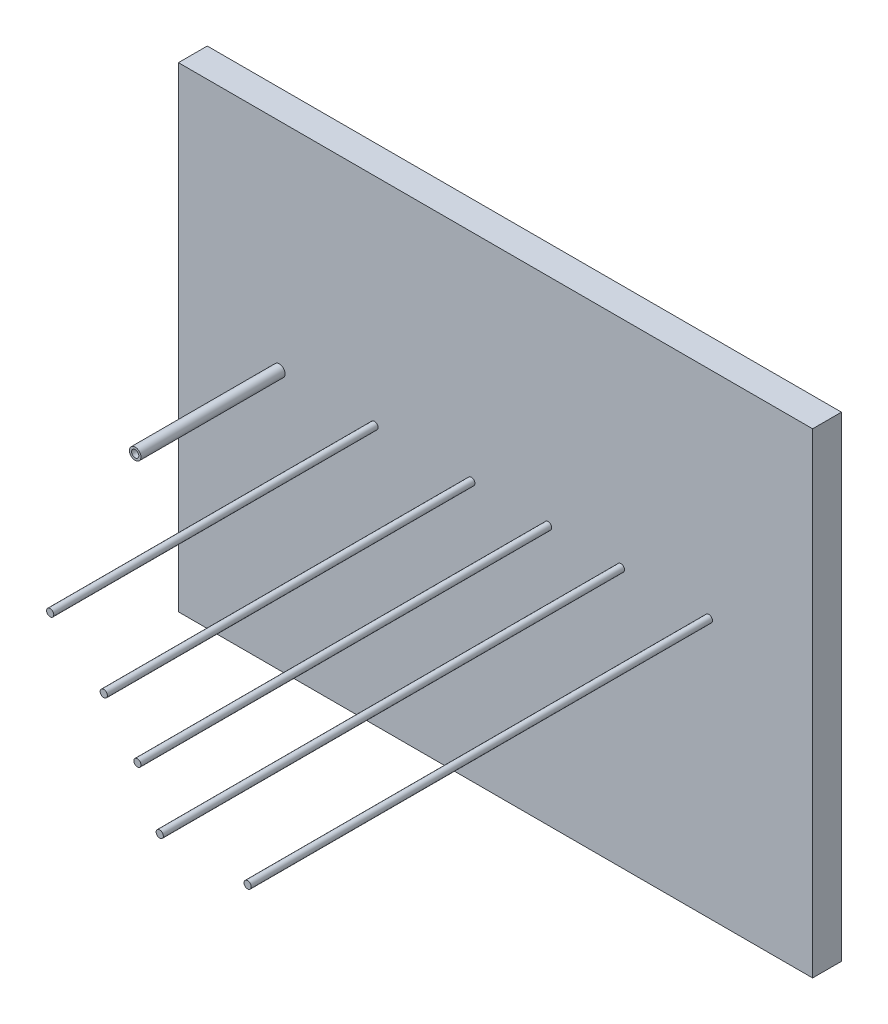
SolidWorks part; units mm, degrees
ref_plane "Alzado" through (0, 0, 0) normal (0, 0, 1) x (1, 0, 0)
ref_plane "Planta" through (0, 0, 0) normal (0, 1, 0) x (1, 0, 0)
ref_plane "Vista lateral" through (0, 0, 0) normal (1, 0, 0) x (0, 0, -1)
sketch "Croquis1" plane through (0, 0, 0) normal (0, 0, 1) x (1, 0, 0)
  line L1 (0, 0) -> (440, 0)
  line L2 (0, 0) -> (0, 330)
  line L3 (0, 330) -> (440, 330)
  line L4 (440, 0) -> (440, 330)
  line L5 (0, 0) -> (440, 330) construction
  line L6 (0, 330) -> (440, 0) construction
  point P4 (220, 165)
  dimension "D1" = 330
  dimension "D2" = 440
extrude "Saliente-Extruir1" add sketch "Croquis1" along normal blind 20
sketch "Croquis3" plane through (0, 0, 20) normal (0, 0, 1) x (1, 0, 0)
  line L0 (0, 0) -> (440, 0) construction
  line L1 (0, 330) -> (0, 0) construction
  circle A0 centre (70, 180) radius 4
  circle A1 centre (136, 180) radius 2.5
  circle A2 centre (203.2, 180) radius 2.5
  circle A4 centre (256.5, 180) radius 2.5
  circle A5 centre (307, 180) radius 2.5
  circle A6 centre (368, 180) radius 2.5
  dimension "D1" = 8
  dimension "D2" = 5
  dimension "D3" = 5
  dimension "D4" = 5
  dimension "D10" = 5
  dimension "D12" = 5
  dimension "D5" = 66
  dimension "D6" = 67.2
  dimension "D8" = 180
  dimension "D7" = 53.3
  dimension "D9" = 70
  dimension "D11" = 50.5
  dimension "D13" = 61
extrude "Saliente-Extruir2" add sketch "Croquis3" along normal blind 100 contours A0 region at (70, 180, 20)
sketch "Croquis5" plane through (0, 0, 120) normal (0, 0, 1) x (1, 0, 0)
  circle A0 centre (70, 180) radius 2.5
  dimension "D1" = 5
extrude "Cortar-Extruir2" cut sketch "Croquis5" against normal blind 100
extrude "Saliente-Extruir3" add sketch "Croquis3<3>" along normal blind 225 contours A1
sketch "Croquis3<3>" plane through (0, 0, 20) normal (0, 0, 1) x (1, 0, 0) same geometry as "Croquis3"
extrude "Saliente-Extruir4" add sketch "Croquis3<4>" along normal blind 255 contours A2
sketch "Croquis3<4>" plane through (0, 0, 20) normal (0, 0, 1) x (1, 0, 0) same geometry as "Croquis3"
extrude "Saliente-Extruir5" add sketch "Croquis3<5>" along normal blind 255 contours A2
sketch "Croquis3<5>" plane through (0, 0, 20) normal (0, 0, 1) x (1, 0, 0) same geometry as "Croquis3"
extrude "Saliente-Extruir6" add sketch "Croquis3<6>" along normal blind 285 contours A4
sketch "Croquis3<6>" plane through (0, 0, 20) normal (0, 0, 1) x (1, 0, 0) same geometry as "Croquis3"
extrude "Saliente-Extruir7" add sketch "Croquis3<7>" along normal blind 320 contours A5 | A6
sketch "Croquis3<7>" plane through (0, 0, 20) normal (0, 0, 1) x (1, 0, 0) same geometry as "Croquis3"
equation "\"DistEjes1\"= 66"
equation "\"D5@Croquis3\"=\"DistEjes1\""
equation "\"DistEjes2\"= 67.2"
equation "\"D6@Croquis3\"=\"DistEjes2\""
equation "\"DistEjes3\"= 53.3"
equation "\"DistVertEjes\"=186.529"
equation "\"D7@Croquis3\"=\"DistEjes3\""
equation "\"DistHorEjes\"=63.0918"
equation "\"DistEjes4\"=50.5"
equation "\"D11@Croquis3\"=\"DistEjes4\""
equation "\"DistEjes5\"= 61"
equation "\"D13@Croquis3\"=\"DistEjes5\""
equation "\"LargoBase\"=330"
equation "\"D1@Croquis1\"=\"LargoBase\""
equation "\"AnchoBase\"= 440"
equation "\"D2@Croquis1\"=\"AnchoBase\""
